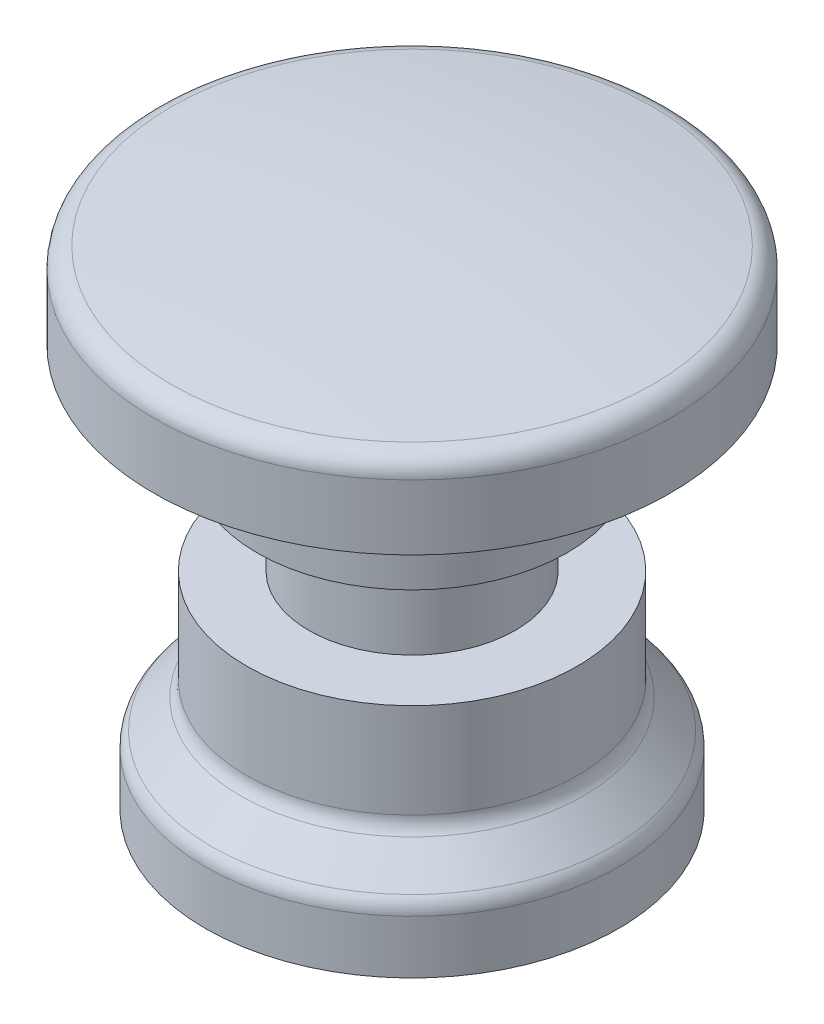
SolidWorks part; units mm, degrees
ref_plane "Front Plane" through (0, 0, 0) normal (0, 0, 1) x (1, 0, 0)
ref_plane "Top Plane" through (0, 0, 0) normal (0, 1, 0) x (1, 0, 0)
ref_plane "Right Plane" through (0, 0, 0) normal (1, 0, 0) x (0, 0, -1)
sketch "Sketch1" plane through (0, 0, 0) normal (0, 0, 1) x (1, 0, 0)
  line L0 (0, 23.5) -> (12.5, 23.5)
  line L1 (12.5, 23.5) -> (12.5, 19.5)
  line L2 (12.5, 19.5) -> (7.5, 19.5)
  line L3 (7.5, 19.5) -> (7.5, 14.5)
  line L4 (7.5, 14.5) -> (5, 14.5)
  line L5 (5, 14.5) -> (5, 10)
  line L6 (5, 10) -> (8, 10)
  line L7 (8, 10) -> (8, 5)
  line L8 (8, 5) -> (10, 3)
  line L9 (10, 3) -> (10, 0)
  line L10 (10, 0) -> (0, 0)
  line L11 (0, 0) -> (0, 23.5)
  dimension "D1" = 12.5
  dimension "D2" = 4
  dimension "D3" = 3
  dimension "D4" = 135
  dimension "D5" = 10
  dimension "D6" = 5
  dimension "D7" = 8
  dimension "D8" = 23.5
  dimension "D9" = 5
  dimension "D10" = 7.5
  dimension "D11" = 5
revolve "Revolve1" add sketch "Sketch1" angle 360 about L11
dome "Dome1" faces to dome 1 distance 1 reverse direction no elliptical dome no face at (0, 23.5, -12.5) parameters "D1"=1
fillet "Fillet1" radius 1 3 edges at (0, 3, -10) (0, 5, -8) (0, 23.5, -12.5)
